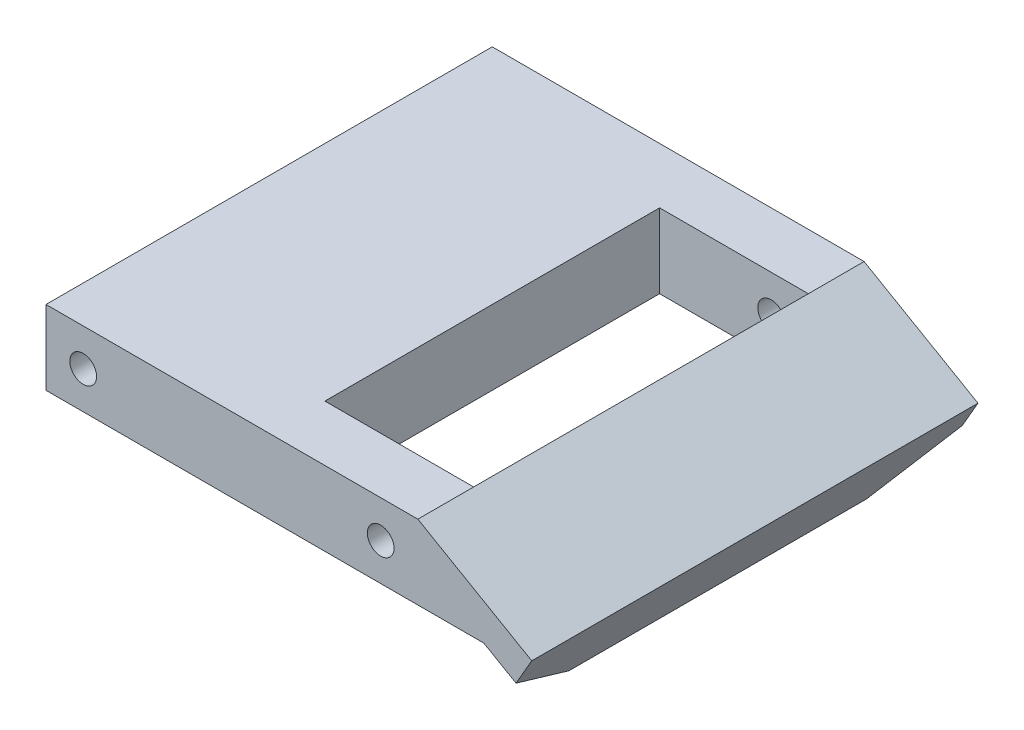
SolidWorks part; units mm, degrees
ref_plane "Front Plane" through (0, 0, 0) normal (0, 0, 1) x (1, 0, 0)
ref_plane "Top Plane" through (0, 0, 0) normal (0, 1, 0) x (1, 0, 0)
ref_plane "Right Plane" through (0, 0, 0) normal (1, 0, 0) x (0, 0, -1)
sketch "Sketch1" plane through (0, 0, 0) normal (0, 0, 1) x (1, 0, 0)
  line L0 (0, 0) -> (63.5, 0)
  line L1 (63.5, 0) -> (82.9448, -11.2265)
  line L2 (82.9448, -11.2265) -> (76.5948, -22.225)
  line L3 (76.5948, -22.225) -> (60.097, -12.7)
  line L4 (60.097, -12.7) -> (0, -12.7)
  line L5 (0, -12.7) -> (0, 0)
  dimension "D1" = 12.7
  dimension "D2" = 12.7
  dimension "D3" = 210
  dimension "D4" = 63.5
  dimension "D5" = 19.05
extrude "Boss-Extrude1" add sketch "Sketch1" along normal blind 76.2
sketch "Sketch2" plane through (0, 0, 0) normal (0, 0, -1) x (-1, 0, 0)
  line L1 (0, -12.7) -> (-60.097, -12.7) construction
  line L2 (0, 0) -> (0, -12.7) construction
  circle A0 centre (-6.35, -6.35) radius 2.286
  dimension "D1" = 4.572
  dimension "D3" = 6.35
  dimension "D2" = 6.35
extrude "Cut-Extrude1" cut sketch "Sketch2" against normal blind 12.7
sketch "Sketch3" plane through (67.0698, -38.7228, 0) normal (0.866, -0.5, 0) x (0, 0, -1)
  line L0 (-76.2, 26.3823) -> (-63.5, 19.05)
  line L1 (-76.2, 19.05) -> (-76.2, 31.75) construction
  line L2 (-76.2, 19.05) -> (0, 19.05) construction
  line L3 (-63.5, 19.05) -> (-76.2, 19.05)
  line L4 (-76.2, 19.05) -> (-76.2, 26.3823)
  line L5 (-38.1, 31.75) -> (-38.1, -10.9985) construction
  line L6 (-76.2, 31.75) -> (0, 31.75) construction
  line L7 (-76.2, -10.9985) -> (0, -10.9985) construction
  line L8 (-12.7, 19.05) -> (0, 19.05)
  line L9 (0, 26.3823) -> (-12.7, 19.05)
  line L10 (0, 19.05) -> (0, 26.3823)
  dimension "D1" = 30
  dimension "D2" = 12.7
extrude "Cut-Extrude2" cut sketch "Sketch3" against normal up to surface (19.05 mm away) up to face at (30.0485, -12.7, 38.1)
sketch "Sketch5" plane through (0, 0, 76.2) normal (0, 0, 1) x (1, 0, 0)
  line L0 (0, 0) -> (0, -12.7) construction
  line L1 (63.5, 0) -> (0, 0) construction
  line L2 (0, -12.7) -> (74.7617, -12.7) construction
  circle A0 centre (6.35, -6.35) radius 2.286
  circle A1 centre (57.15, -6.35) radius 2.286
  dimension "D1" = 4.572
  dimension "D2" = 6.35
  dimension "D3" = 6.35
  dimension "D6" = 4.572
  dimension "D4" = 50.8
  dimension "D5" = 6.35
extrude "Cut-Extrude4" cut sketch "Sketch5" against normal through all
sketch "Sketch6" plane through (0, 0, 0) normal (0, 1, 0) x (1, 0, 0)
  line L0 (63.5, -76.2) -> (63.5, 0) construction
  line L1 (63.5, -9.525) -> (38.1, -9.525)
  line L2 (63.5, -9.525) -> (63.5, -66.675)
  line L3 (63.5, -66.675) -> (38.1, -66.675)
  line L4 (38.1, -9.525) -> (38.1, -66.675)
  line L5 (63.5, -76.2) -> (0, -76.2) construction
  line L6 (63.5, 0) -> (0, 0) construction
  dimension "D1" = 25.4
  dimension "D2" = 9.525
  dimension "D3" = 9.525
extrude "Cut-Extrude5" cut sketch "Sketch6" against normal through all
